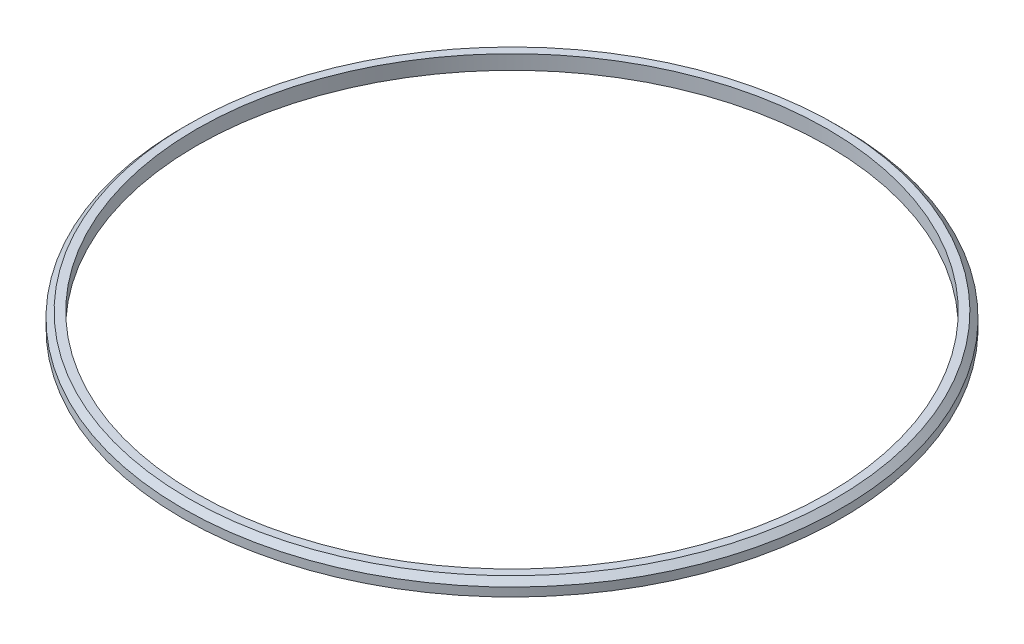
SolidWorks part; units mm, degrees
material "PETG"
ref_plane "Front Plane" through (0, 0, 0) normal (0, 0, 1) x (1, 0, 0)
ref_plane "Top Plane" through (0, 0, 0) normal (0, 1, 0) x (1, 0, 0)
ref_plane "Right Plane" through (0, 0, 0) normal (1, 0, 0) x (0, 0, -1)
sketch "Sketch1" plane through (0, 0, 0) normal (0, 1, 0) x (1, 0, 0)
  circle A0 centre (0, 0) radius 57.2125
  circle A1 centre (0, 0) radius 54.7875
  dimension "Ring OD" = 114.425
  dimension "Ring ID" = 109.575
extrude "Boss-Extrude1" add sketch "Sketch1" along normal blind 2.5
chamfer "Chamfer1" distance 1 angle 45 1 edges at (0, 2.5, 57.2125)
equation "\"tol_dia_id_intfc\" = 0.0500mm ' For hole diameters - Interference fit"
equation "\"tol_dia_id_slip\"  = 0.0750mm ' For hole diameters - Slip fit"
equation "\"tol_dia_id_clear\" = 0.1000mm ' For hole diameters - Clearance fit"
equation "\"tol_dia_od_intfc\" = 0.0500mm ' For shaft diameters - Interference fit"
equation "\"tol_dia_od_slip\"  = 0.0750mm ' For shaft diameters - Slip fit"
equation "\"tol_dia_od_clear\" = 0.1000mm ' For shaft diameters - Clearance fit"
equation "\"tol_general_intfc\"= 0.0250mm ' For general parts (Horiz) - Interference fit"
equation "\"tol_general_slip\" = 0.0375mm ' For general parts (Horiz) - Slip fit"
equation "\"tol_general_clear\"= 0.0500mm ' For general parts (Horiz) - Clearance fit"
equation "\"tol_layer_intfc\"  = 0.0250mm ' For all parts (Vert) - Interference fit"
equation "\"tol_layer_slip\"   = 0.0375mm ' For all parts (Vert) - Slip fit"
equation "\"tol_layer_clear\"  = 0.0500mm ' For all parts (Vert) - Clearance fit"
equation "\"tol_corner_rad\"   = 0.100mm ' For corners that fit into other parts"
equation "\"Ring OD@Sketch1\"= 114.50mm - \"tol_dia_od_slip\""
equation "\"Ring ID@Sketch1\" = 114.5 - ( 2.5 * 2 ) + \"tol_dia_id_slip\""
